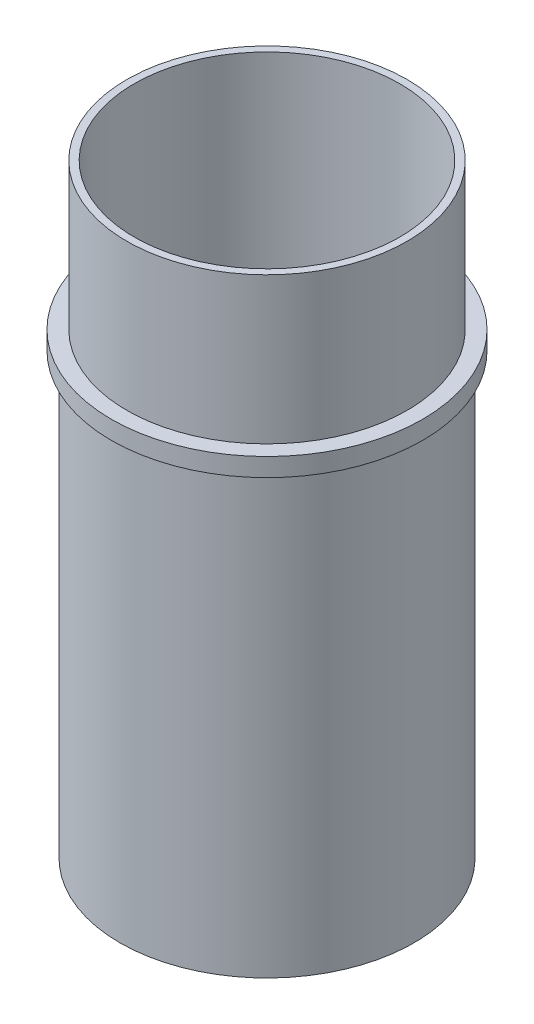
SolidWorks part; units mm, degrees
material "6061 Alloy"
ref_plane "Front Plane" through (0, 0, 0) normal (0, 0, 1) x (1, 0, 0)
ref_plane "Top Plane" through (0, 0, 0) normal (0, 1, 0) x (1, 0, 0)
ref_plane "Right Plane" through (0, 0, 0) normal (1, 0, 0) x (0, 0, -1)
sketch "Sketch1" plane through (0, 0, 0) normal (0, 0, 1) x (1, 0, 0)
  line L0 (0, 0) -> (0, 29.1323) construction
  line L1 (23.0403, -25.8135) -> (23.0403, 78.9615) construction
  line L2 (23.0403, 53.5615) -> (26.9875, 53.5615)
  line L4 (23.0403, 53.5615) -> (26.9875, 53.5615)
  line L7 (23.0403, 53.5615) -> (25.5143, 53.5615)
  line L8 (23.0403, 53.5615) -> (23.0403, -25.8135)
  line L9 (23.0403, -25.8135) -> (25.5143, -25.8135)
  line L10 (25.5143, 53.5615) -> (25.5143, -25.8135)
  line L11 (23.0403, 78.9615) -> (24.3103, 78.9615)
  line L12 (23.0403, 78.9615) -> (23.0403, 53.5615)
  line L13 (23.0403, 53.5615) -> (24.3103, 53.5615)
  line L14 (24.3103, 78.9615) -> (24.3103, 53.5615)
  line L15 (23.0403, 53.5615) -> (26.9875, 53.5615)
  line L16 (23.0403, 53.5615) -> (23.0403, 50.3865)
  line L17 (23.0403, 50.3865) -> (26.9875, 50.3865)
  line L18 (26.9875, 53.5615) -> (26.9875, 50.3865)
  point P18 (23.0403, 50.3865)
revolve "Revolve1" add sketch "Sketch1" angle 360 about L0 region at (23.6753, 66.2615, 0) region at (24.2773, 51.974, 0) region at (24.2773, 12.2865, 0) region at (26.2509, 51.974, 0)
